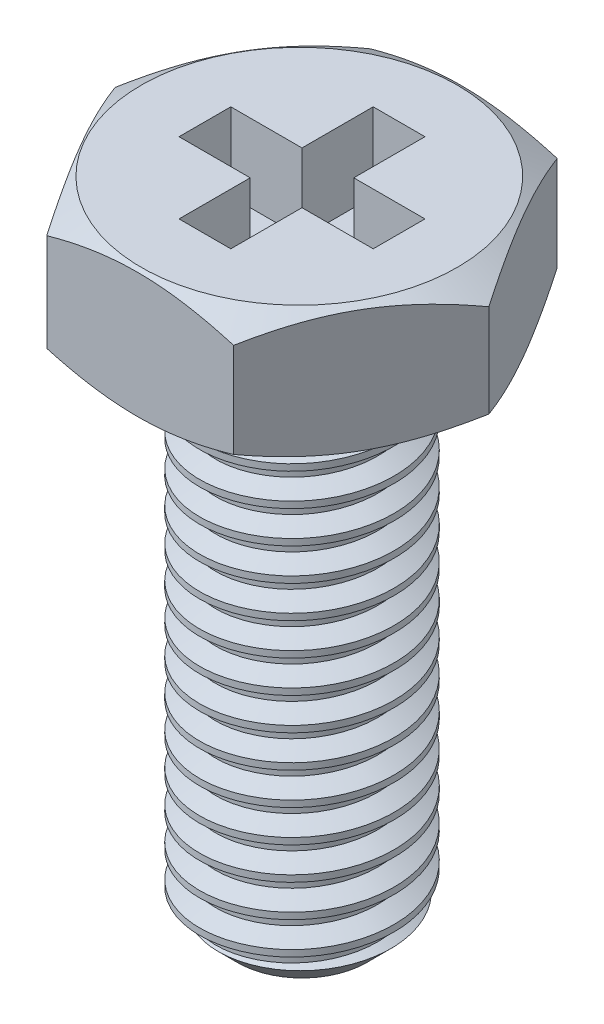
SolidWorks part; units mm, degrees
ref_plane "前基準面" through (0, 0, 0) normal (0, 0, 1) x (1, 0, 0)
ref_plane "上基準面" through (0, 0, 0) normal (0, 1, 0) x (1, 0, 0)
ref_plane "右基準面" through (0, 0, 0) normal (1, 0, 0) x (0, 0, -1)
sketch "草圖3" plane through (0, 0, 0) normal (0, 1, 0) x (1, 0, 0)
  line L1 (1.4434, 2.5) -> (-1.4434, 2.5)
  line L2 (-1.4434, 2.5) -> (-2.8868, 0)
  line L3 (-2.8868, 0) -> (-1.4434, -2.5)
  line L4 (-1.4434, -2.5) -> (1.4434, -2.5)
  line L5 (1.4434, -2.5) -> (2.8868, 0)
  line L6 (2.8868, 0) -> (1.4434, 2.5)
  circle A0 centre (0, 0) radius 2.5 construction
  dimension "D1" = 5
extrude "填料-伸長2" add sketch "草圖3" along normal blind 2
sketch "草圖4" plane through (0, 0, 0) normal (0, 0, 1) x (1, 0, 0)
  line L0 (2.8868, 1) -> (-0.0418, 1) construction
  line L1 (2.8868, 2) -> (2.8868, 0) construction
  line L2 (2.8868, 0) -> (2.8868, 0.2818)
  line L3 (2.8868, 0.2818) -> (2.3987, 0)
  line L4 (1.4434, 0) -> (2.8868, 0) construction
  line L5 (2.3987, 0) -> (2.8868, 0)
  line L6 (2.3987, 2) -> (2.8868, 2)
  line L7 (2.8868, 1.7182) -> (2.3987, 2)
  line L8 (2.8868, 2) -> (2.8868, 1.7182)
  line L9 (-0.0418, 1) -> (-0.0418, 2.6985) construction
  dimension "D1" = 30
revolve "除料-旋轉2" cut sketch "草圖4" angle 360 about L9
sketch "草圖5" plane through (0, 0, 0) normal (0, -1, 0) x (1, 0, 0)
  circle A0 centre (0, 0) radius 1.5
  dimension "D1" = 3
extrude "填料-伸長3" add sketch "草圖5" along normal blind 8
chamfer "導角1" distance 0.5 angle 45 1 edges at (0, -8, -1.5)
sketch "草圖6" plane through (0, -8, 0) normal (0, -1, 0) x (1, 0, 0)
  circle A0 centre (0, 0) radius 1.5 construction
  circle A3 centre (0, 0) radius 1.5
curve "螺旋曲線/渦捲線1" pitch 0.5 height 8 radius 1.5 centre (0, -8, 0) axis (0, 1, 0) start towards (1, 0, 0)
sketch "草圖8" plane through (0, 0, 0) normal (0, 0, 1) x (1, 0, 0)
  line L0 (1.5, -8.2) -> (1.5, -7.8)
  line L5 (1.5, -7.8) -> (1.25, -7.9443)
  line L6 (1.25, -7.9443) -> (1.25, -8.0557)
  line L7 (1.25, -8) -> (1.5, -8) construction
  line L8 (1.5, -8.2) -> (1.25, -8.0557)
  spline S1 degree 3 poles (1.5, -8) (1.5, -7.9896) (1.4219, -7.9687) (1.0883, -7.9375) (0.589, -7.9062) (0, -7.875) (-0.589, -7.8437) (-1.0883, -7.8125) (-1.4219, -7.7812) (-1.5391, -7.75) (-1.4219, -7.7187) (-1.0883, -7.6875) (-0.589, -7.6562) (0, -7.625) (0.589, -7.5937) (1.0883, -7.5625) (1.4219, -7.5312) (1.5391, -7.5) (1.4219, -7.4687) (1.0883, -7.4375) (0.589, -7.4062) (0, -7.375) (-0.589, -7.3437) (-1.0883, -7.3125) (-1.4219, -7.2812) (-1.5391, -7.25) (-1.4219, -7.2188) (-1.0883, -7.1875) (-0.589, -7.1562) (0, -7.125) (0.589, -7.0937) (1.0883, -7.0625) (1.4219, -7.0312) (1.5391, -7) (1.4219, -6.9688) (1.0883, -6.9375) (0.589, -6.9062) (0, -6.875) (-0.589, -6.8437) (-1.0883, -6.8125) (-1.4219, -6.7812) (-1.5391, -6.75) (-1.4219, -6.7188) (-1.0883, -6.6875) (-0.589, -6.6562) (0, -6.625) (0.589, -6.5937) (1.0883, -6.5625) (1.4219, -6.5312) (1.5391, -6.5) (1.4219, -6.4688) (1.0883, -6.4375) (0.589, -6.4062) (0, -6.375) (-0.589, -6.3437) (-1.0883, -6.3125) (-1.4219, -6.2812) (-1.5391, -6.25) (-1.4219, -6.2187) (-1.0883, -6.1875) (-0.589, -6.1562) (0, -6.125) (0.589, -6.0937) (1.0883, -6.0625) (1.4219, -6.0312) (1.5391, -6) (1.4219, -5.9687) (1.0883, -5.9375) (0.589, -5.9062) (0, -5.875) (-0.589, -5.8437) (-1.0883, -5.8125) (-1.4219, -5.7812) (-1.5391, -5.75) (-1.4219, -5.7187) (-1.0883, -5.6875) (-0.589, -5.6562) (0, -5.625) (0.589, -5.5937) (1.0883, -5.5625) (1.4219, -5.5312) (1.5391, -5.5) (1.4219, -5.4687) (1.0883, -5.4375) (0.589, -5.4062) (0, -5.375) (-0.589, -5.3437) (-1.0883, -5.3125) (-1.4219, -5.2812) (-1.5391, -5.25) (-1.4219, -5.2187) (-1.0883, -5.1875) (-0.589, -5.1562) (0, -5.125) (0.589, -5.0937) (1.0883, -5.0625) (1.4219, -5.0312) (1.5391, -5) (1.4219, -4.9687) (1.0883, -4.9375) (0.589, -4.9062) (0, -4.875) (-0.589, -4.8437) (-1.0883, -4.8125) (-1.4219, -4.7812) (-1.5391, -4.75) (-1.4219, -4.7187) (-1.0883, -4.6875) (-0.589, -4.6562) (0, -4.625) (0.589, -4.5937) (1.0883, -4.5625) (1.4219, -4.5312) (1.5391, -4.5) (1.4219, -4.4687) (1.0883, -4.4375) (0.589, -4.4062) (0, -4.375) (-0.589, -4.3437) (-1.0883, -4.3125) (-1.4219, -4.2812) (-1.5391, -4.25) (-1.4219, -4.2187) (-1.0883, -4.1875) (-0.589, -4.1562) (0, -4.125) (0.589, -4.0937) (1.0883, -4.0625) (1.4219, -4.0312) (1.5391, -4) (1.4219, -3.9687) (1.0883, -3.9375) (0.589, -3.9062) (0, -3.875) (-0.589, -3.8437) (-1.0883, -3.8125) (-1.4219, -3.7812) (-1.5391, -3.75) (-1.4219, -3.7187) (-1.0883, -3.6875) (-0.589, -3.6562) (0, -3.625) (0.589, -3.5937) (1.0883, -3.5625) (1.4219, -3.5312) (1.5391, -3.5) (1.4219, -3.4687) (1.0883, -3.4375) (0.589, -3.4062) (0, -3.375) (-0.589, -3.3437) (-1.0883, -3.3125) (-1.4219, -3.2812) (-1.5391, -3.25) (-1.4219, -3.2187) (-1.0883, -3.1875) (-0.589, -3.1562) (0, -3.125) (0.589, -3.0937) (1.0883, -3.0625) (1.4219, -3.0312) (1.5391, -3) (1.4219, -2.9687) (1.0883, -2.9375) (0.589, -2.9062) (0, -2.875) (-0.589, -2.8437) (-1.0883, -2.8125) (-1.4219, -2.7812) (-1.5391, -2.75) (-1.4219, -2.7187) (-1.0883, -2.6875) (-0.589, -2.6562) (0, -2.625) (0.589, -2.5937) (1.0883, -2.5625) (1.4219, -2.5312) (1.5391, -2.5) (1.4219, -2.4687) (1.0883, -2.4375) (0.589, -2.4062) (0, -2.375) (-0.589, -2.3437) (-1.0883, -2.3125) (-1.4219, -2.2812) (-1.5391, -2.25) (-1.4219, -2.2187) (-1.0883, -2.1875) (-0.589, -2.1562) (0, -2.125) (0.589, -2.0937) (1.0883, -2.0625) (1.4219, -2.0312) (1.5391, -2) (1.4219, -1.9687) (1.0883, -1.9375) (0.589, -1.9062) (0, -1.875) (-0.589, -1.8437) (-1.0883, -1.8125) (-1.4219, -1.7812) (-1.5391, -1.75) (-1.4219, -1.7187) (-1.0883, -1.6875) (-0.589, -1.6562) (0, -1.625) (0.589, -1.5937) (1.0883, -1.5625) (1.4219, -1.5312) (1.5391, -1.5) (1.4219, -1.4687) (1.0883, -1.4375) (0.589, -1.4062) (0, -1.375) (-0.589, -1.3437) (-1.0883, -1.3125) (-1.4219, -1.2812) (-1.5391, -1.25) (-1.4219, -1.2187) (-1.0883, -1.1875) (-0.589, -1.1562) (0, -1.125) (0.589, -1.0937) (1.0883, -1.0625) (1.4219, -1.0312) (1.5391, -1) (1.4219, -0.9687) (1.0883, -0.9375) (0.589, -0.9062) (0, -0.875) (-0.589, -0.8437) (-1.0883, -0.8125) (-1.4219, -0.7812) (-1.5391, -0.75) (-1.4219, -0.7187) (-1.0883, -0.6875) (-0.589, -0.6562) (0, -0.625) (0.589, -0.5937) (1.0883, -0.5625) (1.4219, -0.5313) (1.5391, -0.5) (1.4219, -0.4688) (1.0883, -0.4375) (0.589, -0.4063) (0, -0.375) (-0.589, -0.3438) (-1.0883, -0.3125) (-1.4219, -0.2813) (-1.5391, -0.25) (-1.4219, -0.2188) (-1.0883, -0.1875) (-0.589, -0.1563) (0, -0.125) (0.589, -0.0938) (1.0883, -0.0625) (1.4219, -0.0313) (1.5, -0.0104) (1.5, 0) knots 0 0 0 0 0.003906 0.007812 0.011719 0.015625 0.019531 0.023437 0.027344 0.03125 0.035156 0.039062 0.042969 0.046875 0.050781 0.054687 0.058594 0.0625 0.066406 0.070312 0.074219 0.078125 0.082031 0.085937 0.089844 0.09375 0.097656 0.101562 0.105469 0.109375 0.113281 0.117187 0.121094 0.125 0.128906 0.132812 0.136719 0.140625 0.144531 0.148437 0.152344 0.15625 0.160156 0.164062 0.167969 0.171875 0.175781 0.179687 0.183594 0.1875 0.191406 0.195312 0.199219 0.203125 0.207031 0.210937 0.214844 0.21875 0.222656 0.226562 0.230469 0.234375 0.238281 0.242187 0.246094 0.25 0.253906 0.257812 0.261719 0.265625 0.269531 0.273437 0.277344 0.28125 0.285156 0.289062 0.292969 0.296875 0.300781 0.304687 0.308594 0.3125 0.316406 0.320312 0.324219 0.328125 0.332031 0.335937 0.339844 0.34375 0.347656 0.351562 0.355469 0.359375 0.363281 0.367187 0.371094 0.375 0.378906 0.382812 0.386719 0.390625 0.394531 0.398437 0.402344 0.40625 0.410156 0.414062 0.417969 0.421875 0.425781 0.429687 0.433594 0.4375 0.441406 0.445312 0.449219 0.453125 0.457031 0.460937 0.464844 0.46875 0.472656 0.476562 0.480469 0.484375 0.488281 0.492187 0.496094 0.5 0.503906 0.507812 0.511719 0.515625 0.519531 0.523437 0.527344 0.53125 0.535156 0.539062 0.542969 0.546875 0.550781 0.554687 0.558594 0.5625 0.566406 0.570312 0.574219 0.578125 0.582031 0.585937 0.589844 0.59375 0.597656 0.601562 0.605469 0.609375 0.613281 0.617187 0.621094 0.625 0.628906 0.632812 0.636719 0.640625 0.644531 0.648437 0.652344 0.65625 0.660156 0.664062 0.667969 0.671875 0.675781 0.679687 0.683594 0.6875 0.691406 0.695312 0.699219 0.703125 0.707031 0.710937 0.714844 0.71875 0.722656 0.726562 0.730469 0.734375 0.738281 0.742187 0.746094 0.75 0.753906 0.757812 0.761719 0.765625 0.769531 0.773437 0.777344 0.78125 0.785156 0.789062 0.792969 0.796875 0.800781 0.804687 0.808594 0.8125 0.816406 0.820312 0.824219 0.828125 0.832031 0.835937 0.839844 0.84375 0.847656 0.851562 0.855469 0.859375 0.863281 0.867187 0.871094 0.875 0.878906 0.882812 0.886719 0.890625 0.894531 0.898437 0.902344 0.90625 0.910156 0.914062 0.917969 0.921875 0.925781 0.929687 0.933594 0.9375 0.941406 0.945312 0.949219 0.953125 0.957031 0.960937 0.964844 0.96875 0.972656 0.976562 0.980469 0.984375 0.988281 0.992187 0.996094 1 1 1 1 construction
  dimension "D1" = 60
  dimension "D2" = 0.25
  dimension "D3" = 0.4
sweep "除料-掃出1" cut profiles "草圖8" path "螺旋曲線/渦捲線1" align with end faces yes
sketch "草圖9" plane through (0, 2, 0) normal (0, 1, 0) x (1, 0, 0)
  line L0 (-0.4, 0.4) -> (-1.5, 0.4)
  line L1 (-1.5, 0.4) -> (-1.5, -0.4)
  line L2 (-1.5, -0.4) -> (-0.4, -0.4)
  line L3 (-0.4, -0.4) -> (-0.4, -1.5)
  line L4 (-0.4, -1.5) -> (0.4, -1.5)
  line L5 (0.4, -1.5) -> (0.4, -0.4)
  line L6 (0.4, -0.4) -> (1.5, -0.4)
  line L7 (1.5, -0.4) -> (1.5, 0.4)
  line L8 (1.5, 0.4) -> (0.4, 0.4)
  line L9 (0.4, 0.4) -> (0.4, 1.5)
  line L10 (0.4, 1.5) -> (-0.4, 1.5)
  line L11 (-0.4, 1.5) -> (-0.4, 0.4)
  line L12 (-3.2868, 0.4) -> (3.3553, 0.4) construction
  line L13 (-1.5, -0.4) -> (1.5, 0.4) construction
  line L14 (1.5, -0.4) -> (-1.5, 0.4) construction
  point P17 (0, 0)
  dimension "D1" = 0.8
  dimension "D2" = 0.8
  dimension "D3" = 0.8
  dimension "D4" = 0.8
  dimension "D5" = 3
  dimension "D6" = 3
  dimension "D7" = 1.1
  dimension "D8" = 1.1
extrude "除料-伸長1" cut sketch "草圖9" against normal blind 1.2
